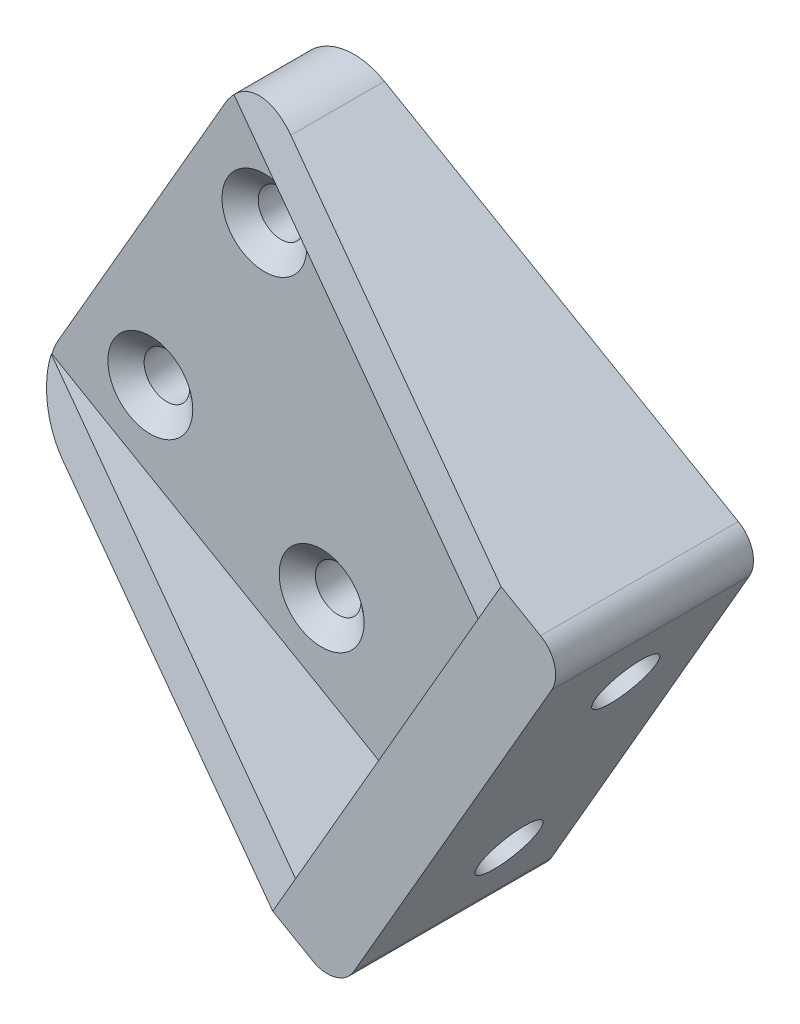
SolidWorks part; units mm, degrees
ref_plane "Front Plane" through (0, 0, 0) normal (0, 0, 1) x (1, 0, 0)
ref_plane "Top Plane" through (0, 0, 0) normal (0, 1, 0) x (1, 0, 0)
ref_plane "Right Plane" through (0, 0, 0) normal (1, 0, 0) x (0, 0, -1)
sketch "Sketch2" plane through (0, 0, 0) normal (0, 0, 1) x (1, 0, 0)
  line L0 (30.6196, -39.6753) -> (66.7608, -60.5414)
  line L1 (50.4064, -18.1036) -> (64.7044, -26.3586) construction
  line L2 (50.4064, -18.1036) -> (40.8814, -34.6014) construction
  line L3 (40.8814, -34.6014) -> (55.1794, -42.8564) construction
  line L4 (64.7044, -26.3586) -> (55.1794, -42.8564) construction
  line L5 (49.6696, -6.6797) -> (30.6196, -39.6753)
  line L6 (49.6696, -6.6797) -> (85.8108, -27.5458)
  line L11 (85.8108, -27.5458) -> (66.7608, -60.5414)
  line L12 (83.6523, -31.2844) -> (78.6523, -39.9446) construction
  dimension "D1" = 38.1
  dimension "D2" = 6.35
extrude "Boss-Extrude1" add sketch "Sketch2" along normal blind 6.35
sketch "Sketch3" plane through (0, 0, 6.35) normal (0, 0, 1) x (1, 0, 0)
  line L0 (80.3115, -24.3708) -> (61.2615, -57.3664)
  line L1 (85.8108, -27.5458) -> (49.6696, -6.6797) construction
  line L2 (30.6196, -39.6753) -> (66.7608, -60.5414) construction
  line L3 (61.2615, -57.3664) -> (66.7608, -60.5414)
  line L4 (66.7608, -60.5414) -> (85.8108, -27.5458)
  line L5 (85.8108, -27.5458) -> (80.3115, -24.3708)
  dimension "D1" = 6.35
extrude "Boss-Extrude2" add sketch "Sketch3" along normal blind 10.16
sketch "Sketch4" plane through (9.525, 16.4978, 0) normal (0.5, 0.866, 0) x (0.866, -0.5, 0)
  line L0 (46.355, -6.35) -> (81.7372, -16.51)
  line L1 (81.7372, -16.51) -> (81.7372, -6.35)
  line L2 (81.7372, -6.35) -> (46.355, -6.35)
extrude "Boss-Extrude3" add sketch "Sketch4" against normal blind 3.81
ref_plane "Plane1" through (0, 0, 0) normal (0.5, 0.866, 0) x (0.866, -0.5, 0)
mirror "Mirror1" about plane through (0, 0, 0) normal (0.5, 0.866, 0) of "Boss-Extrude3"
hole_wizard "Ø5.1 (5.1) Diameter Hole1" positions "Sketch6" profile "Sketch5" hole size "Ø5.1" standard "ANSI Metric"
sketch "Sketch6" plane through (76.2858, -44.0436, 0) normal (0.866, -0.5, 0) x (0, 0, -1)
  point P0 (-6.9373, 9.7331)
  point P3 (-6.9373, -9.7331)
sketch "Sketch5" plane through (81.1523, -35.6145, 6.9373) normal (0, 0, 1) x (0.5, 0.866, 0)
  line L0 (0, 0) -> (0, 9.6602)
  line L1 (0, 9.6602) -> (2.55, 8.128)
  line L2 (2.55, 8.128) -> (2.55, 0)
  line L5 (2.55, 0) -> (0, 0)
  line L10 (0, 9.6602) -> (-2.55, 8.128) construction
  line L11 (0, -6.35) -> (0, 107.95) construction
  dimension "Hole Dia." = 5.1
  dimension "Hole Depth" = 8.128
  dimension "Drill Angle" = 118
hole_wizard "CSK for #6 Flat Head Machine Screw (100)1" positions "Sketch8" profile "Sketch7" countersink size "#6" standard "ANSI Inch" end condition through all
sketch "Sketch8" plane through (0, 0, 6.35) normal (0, 0, 1) x (1, 0, 0)
  point P0 (40.8814, -34.6014)
  point P3 (50.4064, -18.1036)
  point P6 (64.7044, -26.3586)
  point P9 (55.1794, -42.8564)
sketch "Sketch7" plane through (40.8814, -34.6014, 6.35) normal (1, 0, 0) x (0, -1, 0)
  line L0 (0, 0) -> (0, 6.35)
  line L1 (0, 6.35) -> (1.8986, 6.35)
  line L2 (1.8986, 6.35) -> (1.8986, 1.38)
  line L3 (1.8986, 1.38) -> (3.5433, 0)
  line L5 (3.5433, 0) -> (0, 0)
  line L6 (-1.8986, 1.38) -> (-3.5433, 0) construction
  line L11 (0, -6.35) -> (0, 107.95) construction
  dimension "Thru Hole Dia." = 3.7973
  dimension "Thru Hole Depth" = 6.35
  dimension "Near C'Sink Dia." = 7.0866
  dimension "Near C'Sink Angle" = 100
fillet "Fillet1" radius 5.08 2 edges at (49.6696, -6.6797, 3.175) (30.6196, -39.6753, 3.175)
fillet "Fillet2" radius 2.54 2 edges at (85.8108, -27.5458, 8.255) (66.7608, -60.5414, 8.255)
